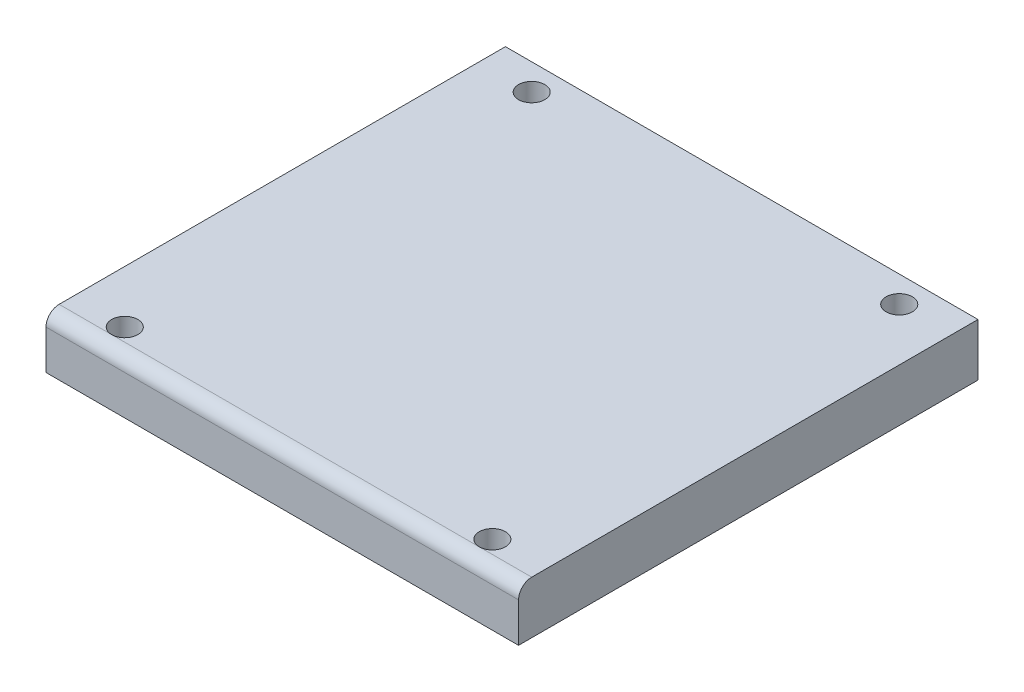
SolidWorks part; units mm, degrees
ref_plane "Płaszczyzna przednia" through (0, 0, 0) normal (0, 0, 1) x (1, 0, 0)
ref_plane "Płaszczyzna górna" through (0, 0, 0) normal (0, 1, 0) x (1, 0, 0)
ref_plane "Płaszczyzna prawa" through (0, 0, 0) normal (1, 0, 0) x (0, 0, -1)
sketch "Szkic1" plane through (0, 0, 0) normal (0, 1, 0) x (1, 0, 0)
  line L0 (-90, -77.5) -> (90, -77.5) construction
  line L1 (90, -87.5) -> (-90, -87.5)
  line L2 (90, -87.5) -> (90, 87.5)
  line L3 (90, 87.5) -> (-90, 87.5)
  line L4 (-90, -87.5) -> (-90, 87.5)
  line L5 (90, -87.5) -> (-90, 87.5) construction
  line L6 (90, 87.5) -> (-90, -87.5) construction
  line L7 (-55, 0) -> (55, 0) construction
  circle A0 centre (-70, -77.5) radius 2.75
  circle A1 centre (70, -77.5) radius 2.75
  circle A2 centre (-70, -77.5) radius 5
  circle A3 centre (70, -77.5) radius 5
  circle A4 centre (70, 77.5) radius 2.75
  circle A5 centre (70, 77.5) radius 5
  circle A6 centre (-70, 77.5) radius 2.75
  circle A7 centre (-70, 77.5) radius 5
  point P0 (0, 0)
  dimension "D3" = 5.5
  dimension "D4" = 5.5
  dimension "D8" = 10
  dimension "D9" = 10
  dimension "D1" = 180
  dimension "D2" = 175
  dimension "D5" = 10
  dimension "D6" = 20
  dimension "D7" = 20
extrude "Dodanie-wyciągnięcie1" add sketch "Szkic1" along normal blind 3 contours L4 L1 L2 L3 A3 A2 A5 A7 | A2 A0 | A7 A6 | A5 A4 | A3 A1 region at (0, 0, 0) region at (-74.8586, 0, 77.5) region at (65.1414, 0, 77.5) region at (65.1414, 0, -77.5) region at (-74.8586, 0, -77.5)
extrude "Dodanie-wyciągnięcie2" add sketch "Szkic1<4>" along normal blind 20 contours L4 L1 L2 L3 A3 A2 A5 A7 region at (0, 0, 0)
sketch "Szkic1<4>" plane through (0, 0, 0) normal (0, 1, 0) x (1, 0, 0) same geometry as "Szkic1"
fillet "Zaokrąglenie1" radius 5 1 edges at (0, 20, 87.5)
